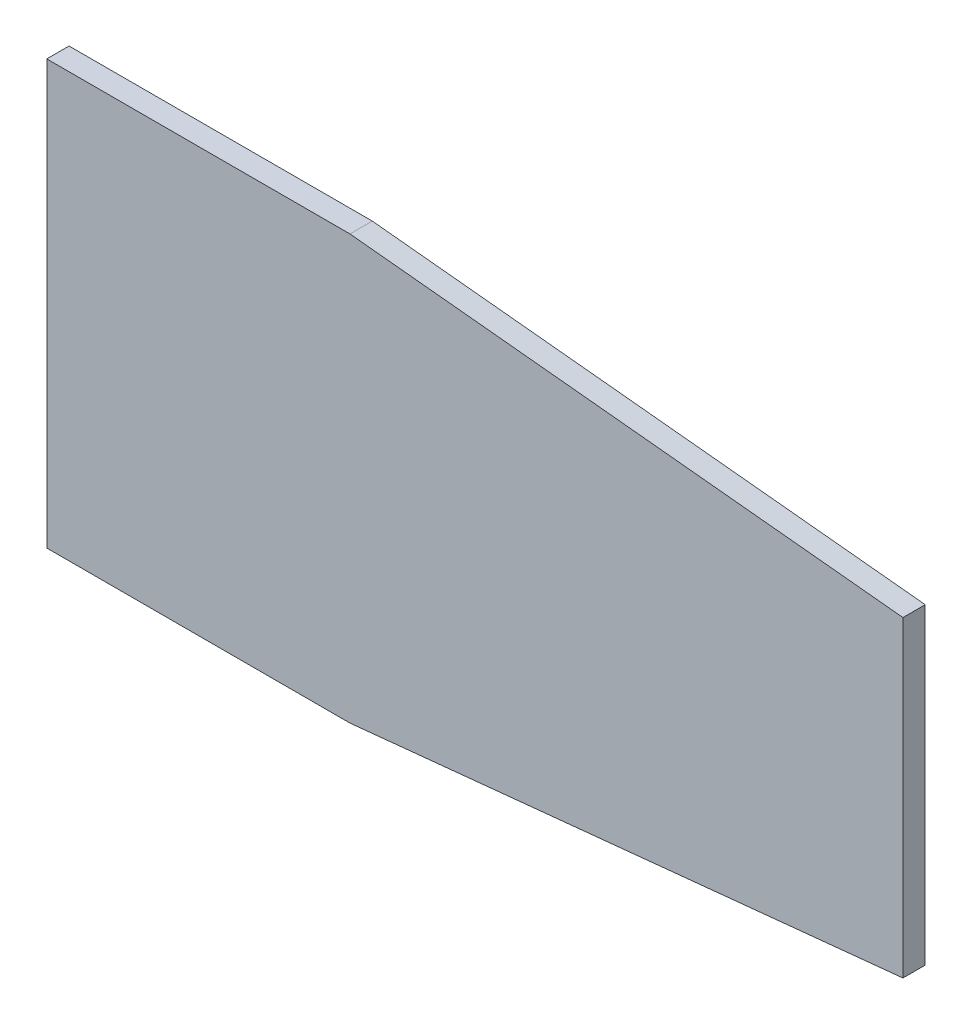
SolidWorks part; units mm, degrees
ref_plane "Ebene vorne" through (0, 0, 0) normal (0, 0, 1) x (1, 0, 0)
ref_plane "Ebene oben" through (0, 0, 0) normal (0, 1, 0) x (1, 0, 0)
ref_plane "Ebene rechts" through (0, 0, 0) normal (1, 0, 0) x (0, 0, -1)
sketch "Skizze1" plane through (0, 0, 0) normal (0, 0, 1) x (1, 0, 0)
  line L0 (0, 0) -> (192, 0) construction
  line L1 (0, -47.5) -> (0, 47.5)
  line L2 (0, 47.5) -> (68, 47.5)
  line L3 (68, 47.5) -> (192, 35)
  line L4 (192, 35) -> (192, -35)
  line L5 (68, -47.5) -> (192, -35)
  line L6 (0, -47.5) -> (68, -47.5)
  dimension "D1" = 95
  dimension "D2" = 192
  dimension "D3" = 70
  dimension "D4" = 124
extrude "Aufsatz-Linear austragen1" add sketch "Skizze1" along normal blind 5
